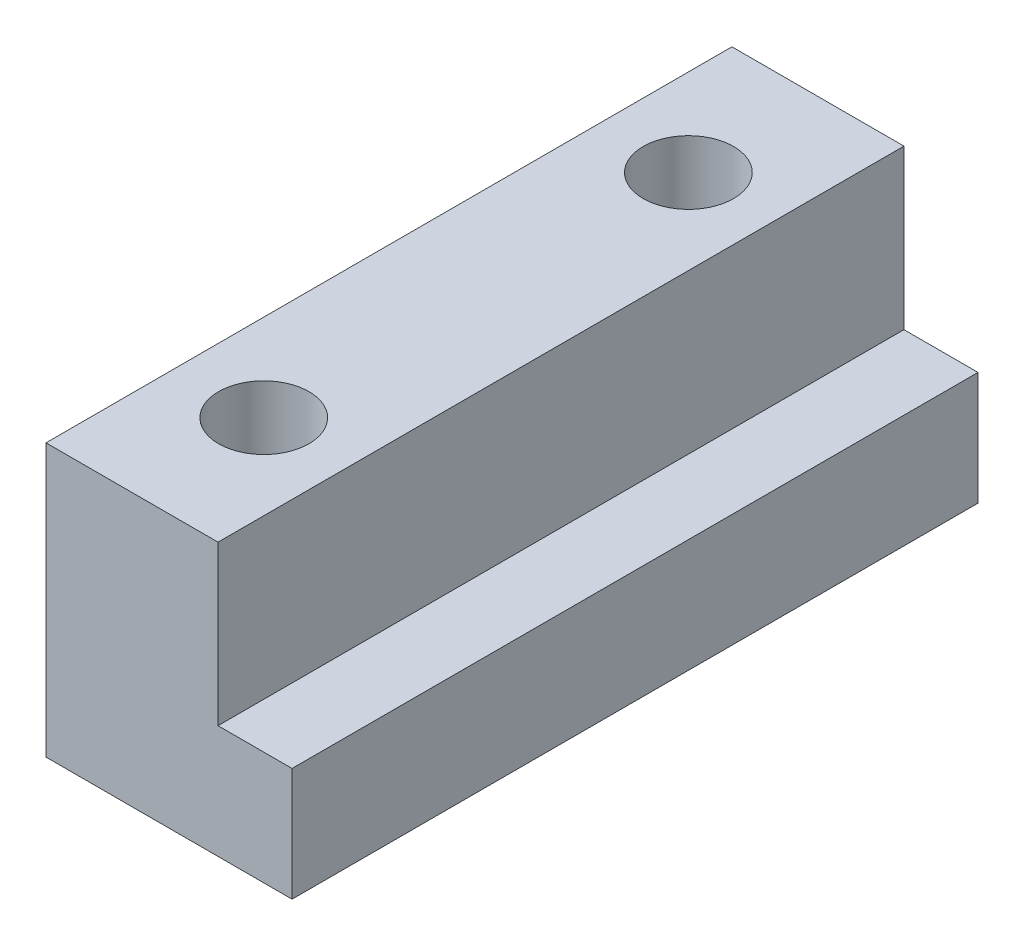
SolidWorks part; units mm, degrees
ref_plane "Front Plane" through (0, 0, 0) normal (0, 0, 1) x (1, 0, 0)
ref_plane "Top Plane" through (0, 0, 0) normal (0, 1, 0) x (1, 0, 0)
ref_plane "Right Plane" through (0, 0, 0) normal (1, 0, 0) x (0, 0, -1)
sketch "Sketch1" plane through (0, 0, 0) normal (0, 0, 1) x (1, 0, 0)
  line L0 (0, 0) -> (0, 12.5)
  line L1 (0, 12.5) -> (7.9, 12.5)
  line L2 (7.9, 12.5) -> (7.9, 5.2)
  line L3 (7.9, 5.2) -> (11.3, 5.2)
  line L4 (11.3, 5.2) -> (11.3, 0)
  line L5 (11.3, 0) -> (0, 0)
  dimension "D1" = 11.3
  dimension "D2" = 12.5
  dimension "D3" = 7.9
  dimension "D4" = 5.2
extrude "Boss-Extrude1" add sketch "Sketch1" against normal blind 31.5
sketch "Sketch2" plane through (0, 12.5, 0) normal (0, 1, 0) x (1, 0, 0)
  line L0 (7.9, 31.5) -> (0, 31.5) construction
  line L1 (0, 31.5) -> (0, 0) construction
  line L2 (7.9, 0) -> (0, 0) construction
  circle A0 centre (4, 6) radius 2.075
  circle A1 centre (4, 25.5) radius 2.075
  dimension "D1" = 4.15
  dimension "D2" = 6
  dimension "D3" = 4
  dimension "D4" = 6
extrude "Cut-Extrude1" cut sketch "Sketch2" against normal blind 7
